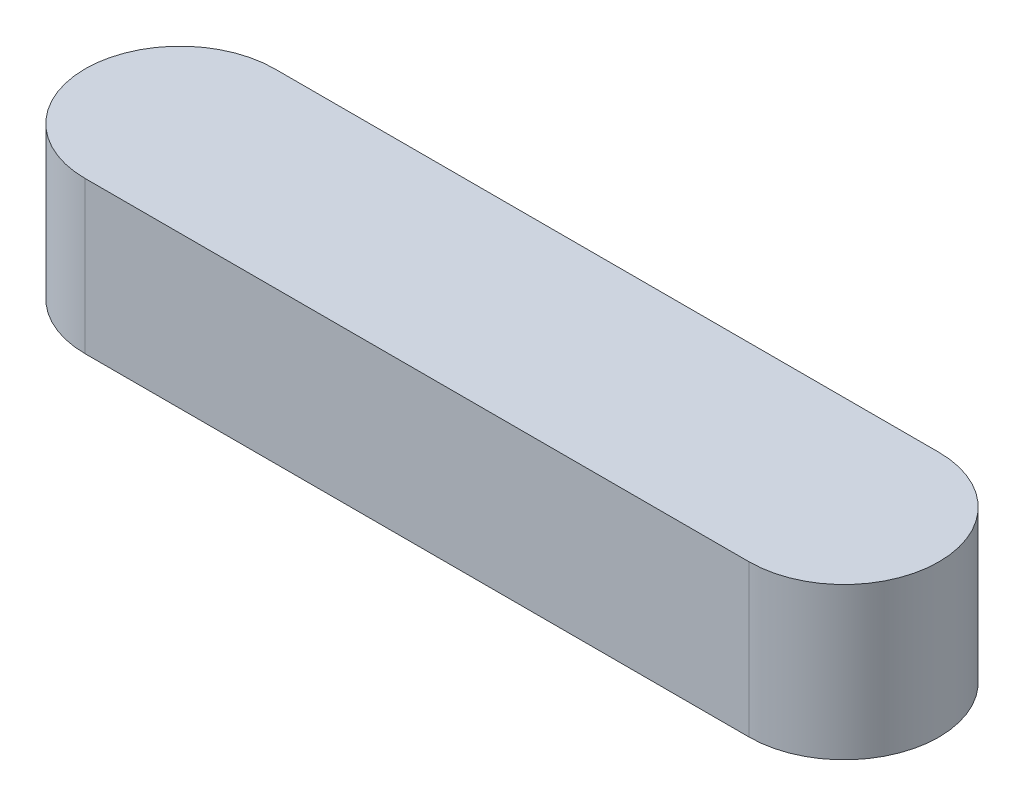
SolidWorks part; units mm, degrees
ref_plane "Front Plane" through (0, 0, 0) normal (0, 0, 1) x (1, 0, 0)
ref_plane "Top Plane" through (0, 0, 0) normal (0, 1, 0) x (1, 0, 0)
ref_plane "Right Plane" through (0, 0, 0) normal (1, 0, 0) x (0, 0, -1)
sketch "Sketch1" plane through (0, 0, 0) normal (0, 1, 0) x (1, 0, 0)
  line L0 (-8.75, 0) -> (8.75, 0) construction
  line L1 (-8.75, -2.5) -> (8.75, -2.5)
  line L2 (-8.75, 2.5) -> (8.75, 2.5)
  line L3 (-11.25, 0) -> (-8.75, 0) construction
  line L4 (8.75, 0) -> (11.25, 0) construction
  circle A0 centre (-8.75, 0) radius 2.5
  circle A1 centre (8.75, 0) radius 2.5
  point P9 (-19.3495, 0)
  dimension "D1" = 5
  dimension "D2" = 22.5
extrude "Boss-Extrude1" add sketch "Sketch1" along normal blind 2 and the other way blind 2 contours A0 L0 A1 L2 | A0 | L0 A0 L1 A1 | A1 region at (0, 0, 0) region at (-8.75, 0, 0) region at (8.75, 0, 0)
